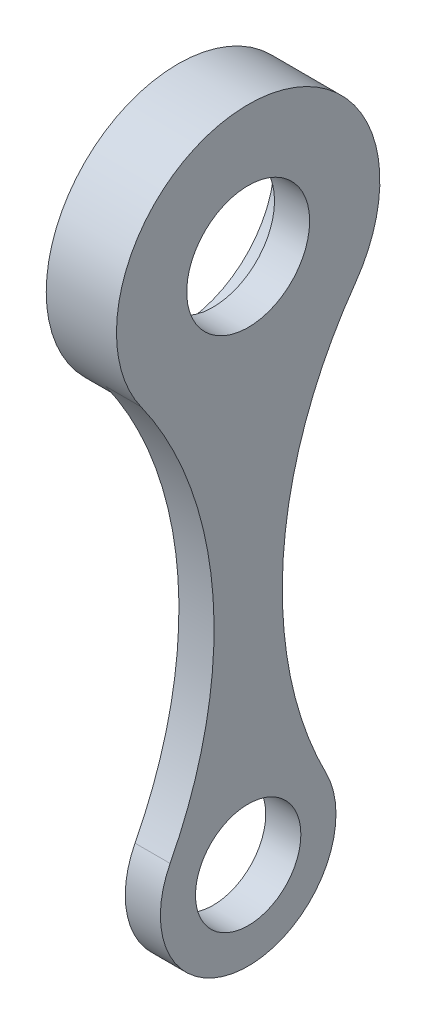
SolidWorks part; units mm, degrees
ref_plane "Front Plane" through (0, 0, 0) normal (0, 0, 1) x (1, 0, 0)
ref_plane "Top Plane" through (0, 0, 0) normal (0, 1, 0) x (1, 0, 0)
ref_plane "Right Plane" through (0, 0, 0) normal (1, 0, 0) x (0, 0, -1)
sketch "Sketch1" plane through (0, 0, 0) normal (1, 0, 0) x (0, 0, -1)
  line L0 (0, 0) -> (0, -150) construction
  circle A0 centre (0, 0) radius 37.5
  circle A1 centre (0, -150) radius 25
  circle A2 centre (0, 0) radius 17.5
  circle A3 centre (0, -150) radius 15
  arc A4 (-30.5557, -21.7394) -> (-22.2217, -138.546) centre (-122.2583, -86.9828) cw
  arc A5 (30.5557, -21.7394) -> (22.2217, -138.546) centre (122.2583, -86.9828) ccw
  point P15 (-10, -78.9734)
  point P16 (10, -78.9734)
  dimension "D1" = 75
  dimension "D2" = 50
  dimension "D5" = 10
  dimension "D6" = 20
  dimension "D3" = 150
  dimension "D4" = 20
extrude "Boss-Extrude1" add sketch "Sketch1" along normal blind 10 contours A2 A0 | L0 A0 A4 A1 | A0 L0 A1 A5 | A1 A3 region at (0, -32.3851, 16.7042) region at (0, -77.9638, -7.6128) region at (0, -77.9638, 7.6128) region at (0, -129.2572, -12.6444)
sketch "Sketch2" plane through (0, 0, 0) normal (-1, 0, 0) x (0, 0, 1)
  circle A0 centre (0, 0) radius 37.5
  circle A1 centre (0, 0) radius 27.5
  dimension "D1" = 10
extrude "Boss-Extrude2" add sketch "Sketch2" along normal blind 10
ref_axis "Axis1" through (10, 0, 0) along (-1, 0, 0)
ref_plane "Plane1" through (5, 0, 0) normal (1, 0, 0) x (0, 0, -1)
ref_point "Point1"
ref_axis "Axis2" through (10, -150, 0) along (-1, 0, 0)
ref_point "Point2"
sketch "Sketch3" plane through (5, 0, 0) normal (1, 0, 0) x (0, 0, -1)
  line L0 (0, 0) -> (0, -150) construction
  point P4 (0, -75)
ref_point "l1"
